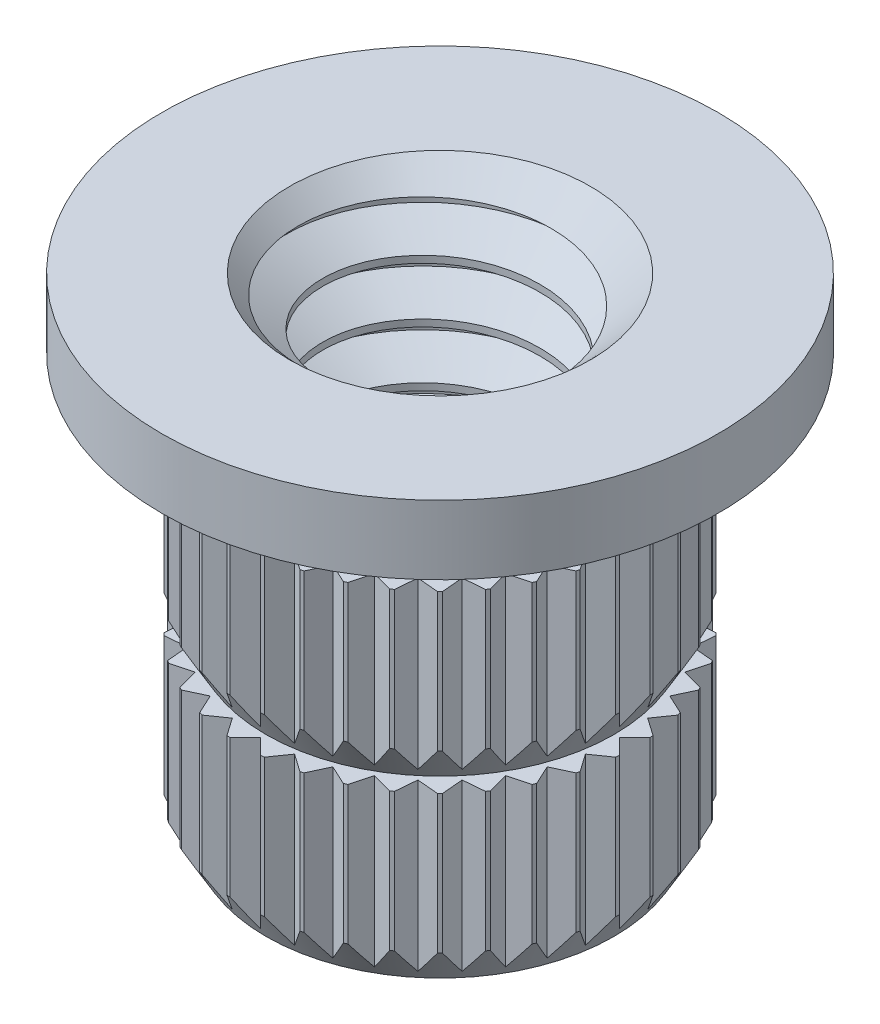
SolidWorks part; units mm, degrees
note: The reader was unsure of these and kept them because the rebuilt part matched: shared geometry of "Sketch1<4>", "Sketch1<3>".
ref_plane "Front Plane" through (0, 0, 0) normal (0, 0, 1) x (1, 0, 0)
ref_plane "Top Plane" through (0, 0, 0) normal (0, 1, 0) x (1, 0, 0)
ref_plane "Right Plane" through (0, 0, 0) normal (1, 0, 0) x (0, 0, -1)
sketch "Sketch0" plane through (0, 0, 0) normal (0, 0, 1) x (1, 0, 0)
  line L0 (0, 0) -> (0, -7.0104) construction
  line L1 (-2.8067, 0) -> (-2.8067, -3.9679) construction
  line L3 (-4.0005, 0) -> (4.0005, 0) construction
  line L5 (-2.5019, -7.0104) -> (0, -7.0104) construction
  line L8 (-2.5019, -7.0104) -> (-2.5019, -4.4958) construction
  line L9 (-2.5019, -4.4958) -> (-4.0005, -1.9001) construction
  line L10 (-4.0005, -1.9001) -> (-4.0005, 0) construction
  line L11 (0, -4.4958) -> (-2.5019, -4.4958) construction
  point P4 (0, -0.9906)
  point P6 (0, -1.9812)
  dimension "D1" = 8.001
  dimension "Length" = 7.0104
  dimension "H" = 0.9906
  dimension "D2" = 5.6134
  dimension "D3" = 5.0038
  dimension "D4" = 2.5146
  dimension "D5" = 5.0292
  dimension "A1" = 30
  dimension "D6" = 0.9906
sketch "Sketch1" plane through (0, 0, 0) normal (0, 1, 0) x (1, 0, 0)
  line L0 (-2.5019, 0) -> (-4.0005, 0) construction
  line L1 (-4.0005, 0) -> (4.0005, 0) construction
  circle A0 centre (0, 0) radius 4.0005
  circle A1 centre (0, 0) radius 2.5019
  circle A2 centre (0, 0) radius 2.8067
  point P6 (2.5019, 0)
extrude "Extrude1" add sketch "Sketch1" against normal up to vertex (7.0104 mm away) contours A1 up to point (0, -7.0104, 0)
extrude "Extrude2" add sketch "Sketch1<4>" against normal up to vertex (3.9679 mm away) from vertex at -1.9812 contours A2 starting at point (0, -1.9812, 0)
sketch "Sketch1<4>" plane through (0, 0, 0) normal (0, 1, 0) x (1, 0, 0) same geometry as "Sketch1"
extrude "Extrude3" add sketch "Sketch1<3>" against normal up to vertex (0.9906 mm away) contours A0 up to point (0, -0.9906, 0)
sketch "Sketch1<3>" plane through (0, 0, 0) normal (0, 1, 0) x (1, 0, 0) same geometry as "Sketch1"
sketch "Sketch2" plane through (0, -3.9679, 0) normal (0, -1, 0) x (1, 0, 0)
  circle A1 centre (0, 0) radius 2.8067
  circle A3 centre (0, 0) radius 2.8067 construction
extrude "Extrude4" add sketch "Sketch2" along normal up to vertex (0.5279 mm away) draft 30 up to point (-2.5019, -4.4958, 0)
sketch "Sketch5" plane through (0, 0, 0) normal (0, 0, 1) x (1, 0, 0)
  line L0 (0, 0) -> (0, -7.0104) construction
  line L1 (0, 0) -> (0, -7.0104) construction
  line L2 (-2.5019, -7.0104) -> (-2.8067, -6.4825)
  line L4 (-2.8067, -6.4825) -> (-2.5019, -6.4825) construction
  line L7 (-2.8067, -3.9679) -> (-2.5019, -4.4958) construction
  line L8 (-2.5019, -6.4825) -> (-2.5019, -7.0104)
  line L9 (-2.8067, -6.4825) -> (-2.8067, -4.4958)
  line L10 (-2.8067, -4.4958) -> (-2.5019, -4.4958)
  line L11 (-2.5019, -4.4958) -> (-2.5019, -6.4825)
sketch "Sketch6" plane through (0, 0, 0) normal (0, 1, 0) x (1, 0, 0)
  circle A2 centre (0, 0) radius 2.0828
  point P0 (-2.0828, 0)
  dimension "Thread OD" = 4.1656
curve "Helix/Spiral1" pitch 0.7937 height 15.7838 radius 2.0828 centre (0, 0, 0) axis (0, -1, 0) start towards (0, 0, 1) parameters "Height"=15.7838, "Pitch"=0.7937
sketch "Sketch7" plane through (0, 0, 0) normal (0, 0, 1) x (1, 0, 0)
  line L0 (-1.4813, 0.7441) -> (-2.1687, 0.3473) construction
  line L1 (-2.1687, 0.3473) -> (-1.4813, -0.0496) construction
  line L2 (-1.4813, -0.0496) -> (-1.4813, 0.7441) construction
  line L3 (-1.4813, 0.3473) -> (-1.5672, 0.3473) construction
  line L4 (-1.5672, 0.3473) -> (-2.0828, 0.3473) construction
  line L5 (-2.0828, 0.3473) -> (-2.1687, 0.3473) construction
  line L6 (-2.0828, 0.3969) -> (-2.0828, 0.2977)
  line L7 (-1.5672, 0) -> (-1.5672, 0.6945) construction
  line L8 (-1.5243, 0.7193) -> (-2.0828, 0.3969)
  line L9 (-1.5243, 0.7193) -> (-1.5243, -0.0248)
  line L10 (-1.5243, -0.0248) -> (-2.0828, 0.2977)
  point P11 (-1.5243, 0.3473)
  dimension "D1" = 0.7937
  dimension "D2" = 0.0992
revolve "Revolve1" add sketch "Sketch5" angle 360 about L0
sketch "Sketch8" plane through (0, 0, 0) normal (0, 1, 0) x (1, 0, 0)
  circle A0 centre (0, 0) radius 1.5672
extrude "Extrude6" cut sketch "Sketch8" against normal up to vertex (7.0104 mm away) up to point (0, -7.0104, 0)
chamfer "Chamfer1" distance 0.5953 angle 45 2 edges at (0, 0, 1.5672) (0, -7.0104, 1.5672)
sweep "Cut-Sweep1" cut profiles "Sketch7" path "Helix/Spiral1"
sketch "Sketch10" plane through (0, -0.9906, 0) normal (0, -1, 0) x (1, 0, 0)
  line L0 (0, 2.5781) -> (-0.2286, 2.8067)
  line L1 (-0.2286, 2.8067) -> (0.2286, 2.8067)
  line L2 (0.2286, 2.8067) -> (0, 2.5781)
  line L5 (0, 2.8067) -> (0, 2.5019) construction
  line L6 (0, 2.5019) -> (0, 2.6543) construction
  line L7 (0, 2.6543) -> (0, 2.5781) construction
  circle A3 centre (0, 0) radius 2.5019 construction
  circle A4 centre (0, 0) radius 2.8067 construction
extrude "Extrude7" cut sketch "Sketch10" along normal through all
pattern_circular "CirPattern1" count 36 over 360 about axis through (0, 0, 0) along (0, 1, 0) of "Extrude7"
equation "\"D1@Sketch7\" = \"Pitch@Helix/Spiral1\""
equation "\"Height@Helix/Spiral1\" = \"Length@Sketch0\" + \"Pitch@Helix/Spiral1\" + (  pi  / 10 ) "
equation "\"D2@Sketch7\" = \"D1@Sketch7\" * 1 / 8"
equation "\"D1@Chamfer1\" = \"Pitch@Helix/Spiral1\" * 6 / 8"
equation "\"D4@Sketch0\" = \"D5@Sketch0\"/2"
equation "\"D6@Sketch0\" = \"H@Sketch0\""
